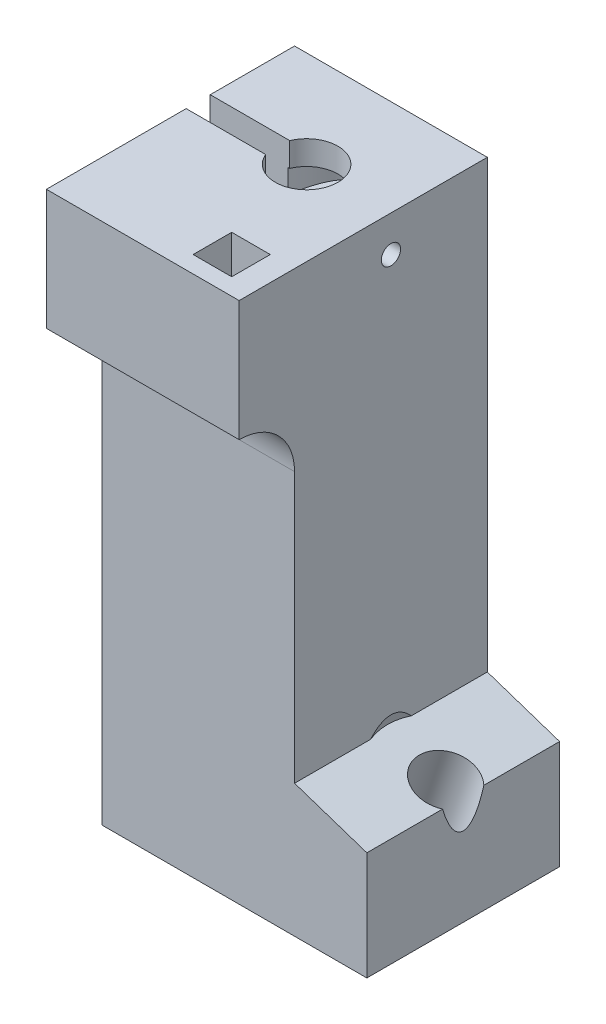
SolidWorks part; units mm, degrees
ref_plane "Front Plane" through (0, 0, 0) normal (0, 0, 1) x (1, 0, 0)
ref_plane "Top Plane" through (0, 0, 0) normal (0, 1, 0) x (1, 0, 0)
ref_plane "Right Plane" through (0, 0, 0) normal (1, 0, 0) x (0, 0, -1)
sketch "VerticalAxis" plane through (0, 0, 0) normal (0, 0, 1) x (1, 0, 0)
  line L0 (0, 0) -> (0, 42.951) construction
sketch "MainRotationalDesign" plane through (13.9419, 0, 0) normal (0, 0, -1) x (0, -1, 0)
  line L2 (5, 13.9419) -> (26.7642, 13.9419) construction
  line L3 (0, 13.9419) -> (-19.7322, 13.9419)
  line L4 (-7.75, 13.9419) -> (-7.75, 7.1919)
  point P0 (0, 13.9419)
  dimension "D4" = 7.75
  dimension "D3" = 6.75
ref_plane "SingleChannelBasePlane" through (0, 7.75, 0) normal (0, 1, 0) x (0.9967, 0, 0.0811)
sketch "ShuttleOutline" plane through (-33.8949, 7.75, -2.7565) normal (0, 1, 0) x (0.9967, 0, 0.0811)
  line L0 (33.946, 0.7475) -> (38.9052, 1.4518) construction
  line L3 (39.0755, -0.6413) -> (34.0676, -0.7475) construction
  line L4 (36.4256, 1.0997) -> (36.9215, 1.1701)
  line L7 (36.9215, 1.1701) -> (36.9515, 0.8013)
  line L8 (36.4256, 1.0997) -> (33.9338, 0.897)
  line L9 (36.4256, 1.0997) -> (36.5715, -0.6944) construction
  line L10 (36.5715, -0.6944) -> (34.0797, -0.897)
  line L11 (33.9338, 0.897) -> (34.0797, -0.897) construction
  line L12 (36.9191, 1.2) -> (37.4175, 1.2405) construction
  line L13 (36.9191, 1.2) -> (36.9515, 0.8013) construction
  line L14 (36.9515, 0.8013) -> (37.4499, 0.8419)
  line L15 (37.4175, 1.2405) -> (37.4499, 0.8419)
  line L16 (37.5407, -0.2745) -> (37.0423, -0.315)
  line L17 (37.5407, -0.2745) -> (37.5731, -0.6731)
  line L18 (37.5731, -0.6731) -> (37.0747, -0.7137) construction
  line L19 (37.0423, -0.315) -> (37.0747, -0.7137) construction
  line L21 (36.5715, -0.6944) -> (37.0723, -0.6838)
  line L22 (37.0723, -0.6838) -> (37.0423, -0.315)
  line L23 (37.4175, 1.2405) -> (38.9052, 1.4518)
  line L24 (39.0755, -0.6413) -> (37.5731, -0.6731)
  line L25 (37.3414, 0.2712) -> (32.4051, -0.1303) construction
  line L26 (38.9052, 1.4518) -> (39.0755, -0.6413) construction
  line L27 (33.946, 0.7475) -> (34.0676, -0.7475) construction
  line L31 (34.0068, 0) -> (40.7346, 0.5471) construction
  circle A2 centre (38.9903, 0.4053) radius 0.6 construction
  circle A3 centre (38.9903, 0.4053) radius 0.4 construction
  circle A4 centre (34.0068, 0) radius 0.35 construction
  circle A5 centre (38.9903, 0.4053) radius 1.05 construction
  circle A6 centre (34.0068, 0) radius 0.75 construction
  arc A7 (33.9338, 0.897) -> (34.0797, -0.897) centre (34.0068, 0) ccw
  arc A8 (38.9052, 1.4518) -> (39.0755, -0.6413) centre (38.9903, 0.4053) cw
  point P4 (37.0723, -0.6838)
  point P15 (34.0068, 0)
  point P16 (36.9215, 1.1701)
  dimension "D2" = 1.2
  dimension "D3" = 0.8
  dimension "D4" = 0.7
  dimension "D1" = 1.5
  dimension "D5" = 2.1
  dimension "D6" = 5
  dimension "D10" = 1.8
  dimension "D9" = 2.5
  dimension "D11" = 2.5
  dimension "D12" = 0.5
  dimension "D14" = 1.5
  dimension "D7" = 0.4
sketch "ShuttleChannelOutline" plane through (33.8949, 7.75, 2.7565) normal (0, -1, 0) x (-0.9967, 0, -0.0811)
  line L0 (29.1854, 2.3987) -> (28.8611, -1.5881) construction
  line L1 (27.1169, -1.4463) -> (31.1037, -1.7705)
  line L2 (27.1169, -1.4463) -> (27.4411, 2.5405)
  line L3 (27.4411, 2.5405) -> (31.428, 2.2163)
  line L4 (31.1037, -1.7705) -> (31.428, 2.2163)
  line L5 (34.0068, 0) -> (27.279, 0.5471) construction
  line L6 (29.1084, 1.4518) -> (28.9381, -0.6413) construction
  line L8 (-199311.2371, 16211.4774) -> (199377.5178, -16211.3364) construction
  point P13 (27.279, 0.5471)
  point P16 (31.2658, 0.2229)
  dimension "D2" = 4
  dimension "D1" = 4
extrude "ShuttleChannelBody-Extrude" add sketch "ShuttleChannelOutline" against normal blind 10
sketch "Sketch23" plane through (0, 17.75, 0) normal (0, 1, 0) x (0.9959, 0, -0.09)
  line L0 (6.5427, -2.5991) -> (6.9025, 1.3847)
  line L1 (6.9025, 1.3847) -> (2.9188, 1.7445)
  line L2 (2.9188, 1.7445) -> (2.5589, -2.2393)
  line L3 (2.5589, -2.2393) -> (6.5427, -2.5991)
  line L4 (2.5589, -2.2393) -> (2.9188, 1.7445) construction
  circle A0 centre (4.9797, -0.4498) radius 0.425
  dimension "D1" = 0.85
extrude "ShuttleChannelCap-Extrude1" add sketch "Sketch23" along normal blind 1
sketch "Sketch22" plane through (0, 18.75, 0) normal (0, 1, 0) x (0.9909, 0, -0.1349)
  line L0 (6.4185, -2.8923) -> (2.4551, -2.3527)
  line L1 (2.4551, -2.3527) -> (2.9947, 1.6107)
  line L2 (2.9947, 1.6107) -> (6.9581, 1.0711)
  line L3 (6.9581, 1.0711) -> (6.4185, -2.8923)
  line L4 (5.0959, 0.3659) -> (4.8127, -1.7149) construction
  line L5 (0, 0) -> (6.6883, -0.9106) construction
  circle A0 centre (4.9543, -0.6745) radius 0.65 construction
  ellipse E0 centre (4.9543, -0.6745) end of major axis (5.1297, 0.6136) minor radius 0.65
  dimension "D1" = 1.3
  dimension "D2" = 2.6
extrude "ShuttleChannelCap-Extrude2" add sketch "Sketch22" along normal blind 0.5
sketch "Sketch24" plane through (0, 19.25, 0) normal (0, 1, 0) x (0.9909, 0, -0.1349)
  line L0 (6.4185, -2.8923) -> (6.9581, 1.0711)
  line L1 (6.9581, 1.0711) -> (2.9947, 1.6107)
  line L2 (2.9947, 1.6107) -> (2.4551, -2.3527)
  line L3 (2.4551, -2.3527) -> (6.4185, -2.8923)
  circle A0 centre (4.9543, -0.6745) radius 0.65
  circle A1 centre (4.9543, -0.6745) radius 0.65 construction
extrude "ShuttleChannelCap-Extrude3" add sketch "Sketch24" along normal blind 0.5
sketch "Sketch25" plane through (0, 19.75, 0) normal (0, 1, 0) x (0.9909, 0, -0.1349)
  line L2 (2.9947, 1.6107) -> (2.4551, -2.3527) construction
  line L4 (2.7586, -0.1233) -> (4.3935, -0.3458)
  line L5 (4.3935, -0.3458) -> (4.3261, -0.8413)
  line L6 (4.3261, -0.8413) -> (2.6911, -0.6187)
  line L7 (2.6911, -0.6187) -> (2.7586, -0.1233)
  circle A0 centre (4.9543, -0.6745) radius 0.65 construction
  point P2 (2.7249, -0.371)
  dimension "D1" = 0.5
extrude "ShuttleChannelCap-InjectionChannel" cut sketch "Sketch25" against normal up to surface (1 mm away) up to face at (4.575, 18.75, 0)
sketch "Sketch26" plane through (6.75, 0, 0) normal (-1, 0, 0) x (0, -0.8752, -0.4838)
  line L0 (-6.7828, -3.7491) -> (-16.6288, -9.1914) construction
  line L1 (-7.7503, -1.9987) -> (-5.8153, -5.4995) construction
  line L3 (-18.2528, -7.8038) -> (-16.3177, -11.3046) construction
  circle A0 centre (-16.6288, -9.1914) radius 0.2
  dimension "D1" = 0.4
  dimension "D2" = 0.75
extrude "ShuttleChannelCap-InjectionHole" cut sketch "Sketch26" along normal through all
fillet "ShuttleChannelCap-InjectionHole-Fillet" radius 0.25 1 edges at (5.6427, 18.9547, 0.1948)
extrude "Channel-Cut-Extrude12" cut sketch "ShuttleOutline" along normal blind 10 and the other way blind 5
fillet "Fillet1" radius 0.125 4 edges at (3, 12.75, 0.56) (3.5, 12.75, 0.56) (3.5, 12.75, -0.56) (3, 12.75, -0.56)
sketch "Sketch27" plane through (0, 0, 2) normal (0, 0, 1) x (1, 0, 0)
  line L0 (6.75, 7.75) -> (8.25, 7.75)
  line L1 (8.25, 7.75) -> (8.25, 9)
  line L2 (8.25, 9) -> (6.75, 9.5)
  line L3 (6.75, 19.75) -> (6.75, 7.75) construction
  line L4 (6.75, 9.5) -> (6.75, 7.75)
  dimension "D1" = 1.5
  dimension "D2" = 1.25
  dimension "D3" = 1.75
extrude "Boss-Extrude1" add sketch "Sketch27" against normal up to surface (4 mm away) up to face at (4.75, 13.75, -2)
ref_plane "MountingHolePlane" through (3.525, 10.575, 0) normal (0.3162, 0.9487, 0) x (0.9487, -0.3162, 0)
sketch "Sketch32" plane through (3.525, 10.575, 0) normal (0.3162, 0.9487, 0) x (0.9487, -0.3162, 0)
  line L0 (4.9806, 2) -> (4.9806, -2)
sketch "Sketch31" plane through (0, 0, 2) normal (0, 0, 1) x (1, 0, 0)
  line L0 (8.25, 9) -> (8.25, 10)
  line L1 (8.25, 7.75) -> (8.25, 9) construction
  line L2 (8.25, 10) -> (6.75, 10.5)
  line L3 (6.75, 19.75) -> (6.75, 9.5) construction
  line L4 (6.75, 10.5) -> (6.75, 9.5)
  line L5 (4.35, 10.3) -> (2.7, 10.85) construction
  line L6 (6.75, 9.5) -> (8.25, 9)
  line L7 (8.25, 9) -> (6.75, 9.5) construction
  dimension "D1" = 1
extrude "Boss-Extrude3" add sketch "Sketch31" against normal up to surface (4 mm away) up to face at (5.9167, 12.25, -2)
sketch "Sketch28" plane through (3.525, 10.575, 0) normal (0.3162, 0.9487, 0) x (0.9487, -0.3162, 0)
  line L0 (4.9806, 0) -> (4.2806, 0) construction
  line L1 (4.9806, 2) -> (4.9806, -2) construction
  circle A0 centre (4.2806, 0) radius 0.575
  point P3 (0, 0)
  point P4 (0, 0)
  point P5 (0, 0)
  point P7 (0, 0)
  point P8 (0, 0)
  point P9 (0, 0)
  dimension "D1" = 1.15
  dimension "D2" = 0.7
extrude "Cut-Extrude1" cut sketch "Sketch28" against normal through all and the other way through all contours A0
sketch "Sketch29" plane through (0, 0, 2) normal (0, 0, 1) x (1, 0, 0)
  line L0 (2.75, 19.75) -> (2.75, 7.75) construction
  line L1 (6.75, 19.75) -> (2.75, 19.75)
  line L2 (6.75, 19.75) -> (6.75, 17.25)
  line L3 (6.75, 17.25) -> (2.75, 17.25)
  line L4 (2.75, 19.75) -> (2.75, 17.25)
  dimension "D1" = 2.5
extrude "Boss-Extrude2" add sketch "Sketch29" along normal blind 1.15
fillet "Fillet2" radius 1.15 1 edges at (4.75, 17.25, 2)
sketch "Sketch30" plane through (0, 19.75, 0) normal (0, 1, 0) x (1, 0, 0)
  line L0 (6.75, -2) -> (2.75, -2) construction
  line L1 (6.2452, -2.8) -> (5.4452, -2.8)
  line L2 (6.2452, -2.8) -> (6.2452, -2)
  line L3 (6.2452, -2) -> (5.4452, -2)
  line L4 (5.4452, -2.8) -> (5.4452, -2)
  dimension "D1" = 0.8
extrude "Cut-Extrude2" cut sketch "Sketch30" against normal blind 2
sketch "Sketch33" plane through (3.825, 11.475, 0) normal (0.3162, 0.9487, 0) x (0.9487, -0.3162, 0)
  circle A0 centre (4.2806, 0) radius 1.27
  dimension "D1" = 2.54
extrude "Cut-Extrude4" cut sketch "Sketch33" along normal through all
equation "\"DriveAngle\"= 37.5"
equation "\"WidthExtensionHalfOffset\"= 2.2mm"
equation "\"RotationMarginAngle\"= 17.5deg"
equation "\"Rotation\"= 180 - 2 * \"RotationMarginAngle\""
equation "\"DriveVerticalOffset\"= 5"
equation "\"ShuttleChannelBackWall\"= 1.75"
equation "\"ShuttleHoleSeparation\"=5"
equation "\"D6@ShuttleOutline\"=\"ShuttleHoleSeparation\""
equation "\"ElectrodePathToWall\"= \"ShuttleHoleSeparation\" + \"ShuttleChannelBackWall\""
equation "\"D3@MainRotationalDesign\"=\"ElectrodePathToWall\""
equation "\"ScrewHeadDiameter\"=1.3"
equation "\"D1@Sketch22\"=\"ScrewHeadDiameter\""
equation "\"D2@Sketch22\"=2*\"ScrewHeadDiameter\""
equation "\"ScrewFreeDiameter\"=0.85"
equation "\"D1@Sketch23\"=\"ScrewFreeDiameter\""
equation "\"ChannelWidth\"= 4"
equation "\"D2@ShuttleChannelOutline\"=\"ChannelWidth\""
equation "\"ChannelDepth\"=4"
equation "\"D1@ShuttleChannelOutline\"=\"ChannelDepth\""
equation "\"FullConnectedHeight\"=6"
equation "\"ActualOffset\"=7.75"
equation "\"D4@MainRotationalDesign\"=\"ActualOffset\""
equation "\"LooseTapDrill0_80\"=1.52"
equation "\"EIB_Mount_Screw_Head\"=2.54"
equation "\"TapDrill0_80\"=1.19"
equation "\"StimElectrodeBendAngle\"=24"
equation "\"ChannelTravel\"= 10"
equation "\"D1@ShuttleChannelBody-Extrude\"=\"ChannelTravel\""
equation "\"StimChannelTravel\"= 15"
equation "\"D1\"= \"StimChannelTravel\""
equation "\"D1@Channel-Cut-Extrude12\" = \"ChannelTravel\""
